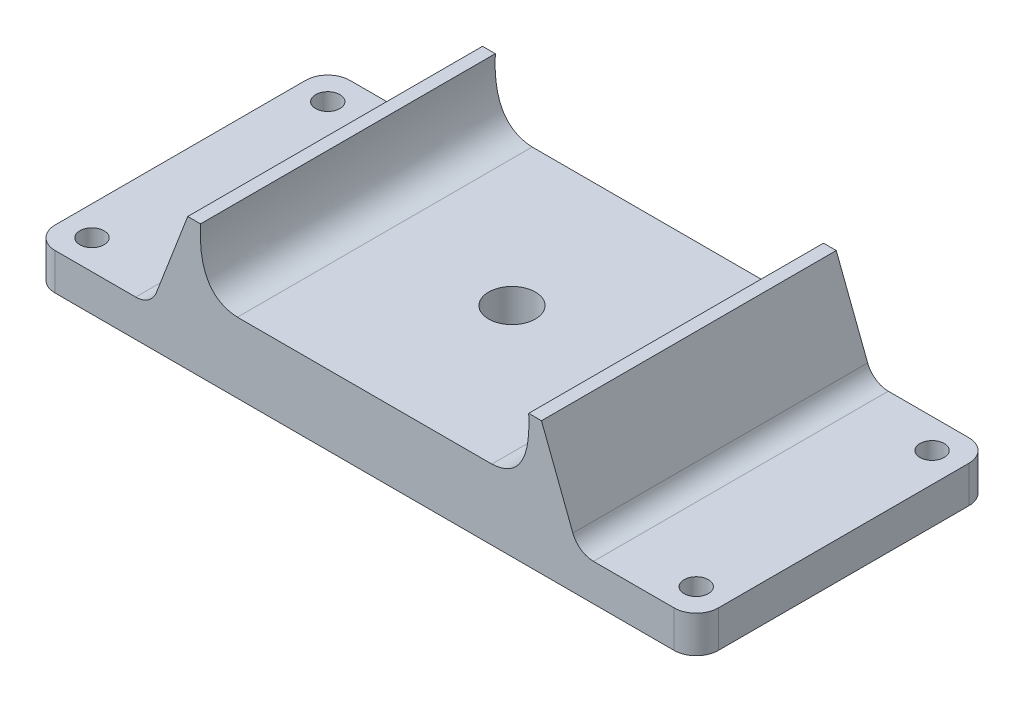
SolidWorks part; units mm, degrees
ref_plane "Front Plane" through (0, 0, 0) normal (0, 0, 1) x (1, 0, 0)
ref_plane "Top Plane" through (0, 0, 0) normal (0, 1, 0) x (1, 0, 0)
ref_plane "Right Plane" through (0, 0, 0) normal (1, 0, 0) x (0, 0, -1)
sketch "Croquis1" plane through (0, 0, 0) normal (0, 1, 0) x (1, 0, 0)
  line L0 (0, 0) -> (-41.9771, 0) construction
  line L1 (-45, 20) -> (45, 20)
  line L2 (-45, 20) -> (-45, -20)
  line L3 (-45, -20) -> (45, -20)
  line L4 (45, 20) -> (45, -20)
  line L5 (-45, 20) -> (45, -20) construction
  line L6 (-45, -20) -> (45, 20) construction
  line L7 (-24, 20) -> (24, 20)
  line L8 (-24, 20) -> (-24, -20)
  line L9 (-24, -20) -> (24, -20)
  line L10 (24, 20) -> (24, -20)
  line L11 (-24, 20) -> (24, -20) construction
  line L12 (-24, -20) -> (24, 20) construction
  line L13 (0, 0) -> (0, 25.1862) construction
  circle A0 centre (0, 0) radius 3.175
  circle A1 centre (-41, 16) radius 1.65
  circle A2 centre (41, 16) radius 1.65
  circle A3 centre (41, -16) radius 1.65
  circle A4 centre (-41, -16) radius 1.65
  point P0 (0, 0)
  dimension "D2" = 6.35
  dimension "D5" = 3.3
  dimension "D1" = 90
  dimension "D3" = 40
  dimension "D4" = 48
  dimension "D6" = 4
  dimension "D7" = 4
extrude "Saliente-Extruir1" add sketch "Croquis1" along normal blind 5 contours L8 L1 L2 L3 | L1 L10 L3 L4 region at (-34.3649, 0, 0) region at (34.3649, 0, 0)
extrude "Saliente-Extruir2" add sketch "Croquis1<3>" along normal blind 18 contours L10 L1 L8 L3 A0 region at (0, 0, -19.3752)
sketch "Croquis1<3>" plane through (0, 0, 0) normal (0, 1, 0) x (1, 0, 0) same geometry as "Croquis1"
sketch "Croquis2" plane through (0, 0, 20) normal (0, 0, 1) x (1, 0, 0)
  line L0 (0, 0) -> (0, 27.1078) construction
  line L1 (-24, 18) -> (24, 18) construction
  line L2 (-17.2629, 9.5338) -> (17.2629, 9.5338)
  line L3 (-22.2664, 18) -> (22.2664, 18)
  spline S0 degree 2 poles (-22.2664, 18) (-22.7015, 9.8197) (-17.2629, 9.5338) knots 0 0 0 1 1 1
  spline S1 degree 2 poles (22.2664, 18) (22.7015, 9.8197) (17.2629, 9.5338) knots 0 0 0 1 1 1
extrude "Cortar-Extruir1" cut sketch "Croquis2" against normal blind 52
chamfer "Chaflán1" distance 5 distance2 13 1 edges at (-24, 5, 0) first distance on face at (-34.5, 5, 0)
chamfer "Chaflán2" distance 13 distance2 5 1 edges at (24, 5, 0) first distance on face at (24, 11.5, 0)
fillet "Redondeo1" radius 3 2 edges at (-29, 5, 0) (29, 5, 0)
fillet "Redondeo2" radius 3 4 edges at (-45, 2.5, -20) (45, 2.5, -20) (45, 2.5, 20) (-45, 2.5, 20)
